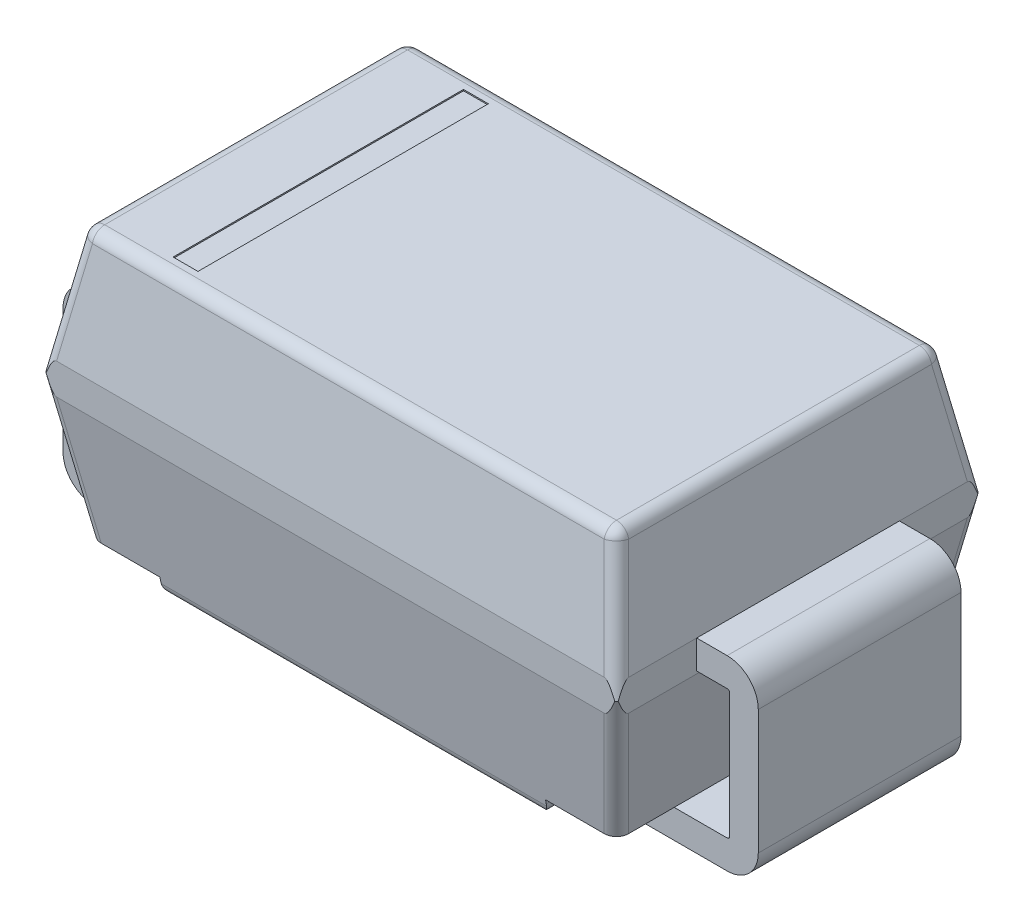
SolidWorks part; units mm, degrees
ref_plane "Front Plane" through (0, 0, 0) normal (0, 0, 1) x (1, 0, 0)
ref_plane "Top Plane" through (0, 0, 0) normal (0, 1, 0) x (1, 0, 0)
ref_plane "Right Plane" through (0, 0, 0) normal (1, 0, 0) x (0, 0, -1)
sketch "Sketch5" plane through (0, 0, 0) normal (0, 0, 1) x (1, 0, 0)
  line L0 (-2.3, 0.3724) -> (-2.3, 0.1224)
  line L1 (-2.3, 0.3724) -> (-2.1413, 1.2724)
  line L2 (2.3, 0.3724) -> (2.3, 0.1224)
  line L3 (0, 0) -> (-0.663, 0) construction
  line L4 (-2.3, 0.1224) -> (-2.1204, -0.896)
  line L5 (2.3, 0.1224) -> (2.1204, -0.896)
  line L6 (2.3, 0.3724) -> (2.1413, 1.2724)
  line L7 (2.3, 0.3724) -> (2.3, 0.1224)
  line L8 (0, 0) -> (0, 0.4546) construction
  line L9 (-2.3, 0.1224) -> (-1.6581, 0.1224) construction
  line L10 (2.1413, 1.2724) -> (-2.1413, 1.2724)
  line L11 (-2.1204, -0.896) -> (-1.55, -0.896)
  line L12 (1.55, -1.0276) -> (-1.55, -1.0276)
  line L13 (-2.3, 0.3724) -> (-2.3, 0.1224)
  line L14 (-1.55, -0.896) -> (-1.55, -1.0276)
  line L15 (1.55, -0.896) -> (1.55, -1.0276)
  line L16 (2.1204, -0.896) -> (1.55, -0.896)
  line L17 (-0.6495, -1.1276) -> (-0.7495, -1.1276) construction
  dimension "D1" = 0.75
  dimension "D2" = 0.1315
  dimension "D3" = 0.25
  dimension "D4" = 10
  dimension "D5" = 10
  dimension "BodyLength" = 4.6
  dimension "D6" = 10
  dimension "D7" = 10
  dimension "Height" = 2.4
  dimension "A1" = 0.1
extrude "Extrude2" add sketch "Sketch5" along normal mid plane 2.92 contours L12 L5 L2 L6 L10 L1 L0 L4 region at (0, 0.144, 0)
sketch "Sketch15" plane through (0, 0, 0) normal (1, 0, 0) x (0, 0, -1)
  line L0 (1.1543, -1.6111) -> (1.46, 0.1224)
  line L1 (1.46, 0.1224) -> (1.46, 0.3724)
  line L2 (1.46, 0.3724) -> (1.1334, 2.2248)
  dimension "D1" = 10
  dimension "D2" = 10
extrude "Extrude10" cut sketch "Sketch15" against normal through all and the other way through all flip side to cut
mirror "Mirror1" about plane through (0, 0, 0) normal (0, 0, 1) of "Extrude10"
sketch "Sketch9" plane through (0, 0, 0) normal (0, 0, 1) x (1, 0, 0)
  line L0 (-2.3, 0.3724) -> (-2.545, 0.3724)
  line L1 (-2.795, 0.1224) -> (-2.795, -0.8776)
  line L2 (-2.545, -1.1276) -> (-1.275, -1.1276)
  line L3 (-2.3, 0.1424) -> (-2.545, 0.1424)
  line L4 (-2.565, 0.1224) -> (-2.565, -0.8776)
  line L5 (-2.545, -0.8976) -> (-1.275, -0.8976)
  line L6 (-1.275, -0.8976) -> (-1.275, -1.1276)
  line L7 (-2.3, 0.3724) -> (-2.3, 0.1424)
  line L8 (0, 0) -> (0, -0.4455) construction
  line L9 (2.3, 0.3724) -> (2.3, 0.1424)
  line L10 (1.275, -0.8976) -> (1.275, -1.1276)
  line L11 (2.545, -0.8976) -> (1.275, -0.8976)
  line L12 (2.565, 0.1224) -> (2.565, -0.8776)
  line L13 (2.3, 0.1424) -> (2.545, 0.1424)
  line L14 (2.545, -1.1276) -> (1.275, -1.1276)
  line L15 (2.795, 0.1224) -> (2.795, -0.8776)
  line L16 (2.3, 0.3724) -> (2.545, 0.3724)
  arc A0 (-2.545, 0.3724) -> (-2.795, 0.1224) centre (-2.545, 0.1224) ccw
  arc A1 (-2.795, -0.8776) -> (-2.545, -1.1276) centre (-2.545, -0.8776) ccw
  arc A2 (-2.545, 0.1424) -> (-2.565, 0.1224) centre (-2.545, 0.1224) ccw
  arc A3 (-2.565, -0.8776) -> (-2.545, -0.8976) centre (-2.545, -0.8776) ccw
  arc A4 (2.565, -0.8776) -> (2.545, -0.8976) centre (2.545, -0.8776) cw
  arc A5 (2.545, 0.1424) -> (2.565, 0.1224) centre (2.545, 0.1224) cw
  arc A6 (2.795, -0.8776) -> (2.545, -1.1276) centre (2.545, -0.8776) cw
  arc A7 (2.545, 0.3724) -> (2.795, 0.1224) centre (2.545, 0.1224) cw
  dimension "D1" = 0.25
  dimension "TotalLength" = 5.59
  dimension "PinLength" = 1.52
  dimension "C" = 0.23
extrude "Extrude6" add sketch "Sketch9" along normal mid plane 1.63
fillet "Fillet1" radius 0.1 28 edges at (0, -1.0276, -1.2572) (-1.55, -1.0276, 1.0361) (-1.55, -1.0276, -1.0361) (0, -1.0276, 1.2572) (1.55, -1.0276, 1.0361) (1.55, -1.0276, -1.0361) (-2.1413, 1.2724, 0) (0, 1.2724, -1.3013) (2.1413, 1.2724, 0) (0, 1.2724, 1.3013) (-2.2102, -0.3868, -1.3702) (-2.2207, 0.8224, -1.3807) (-2.2207, 0.8224, 1.3807) (-2.2102, -0.3868, 1.3702) (2.2102, -0.3868, 1.3702) (2.2207, 0.8224, 1.3807) (2.2102, -0.3868, -1.3702) (2.2207, 0.8224, -1.3807) (1.55, -0.9626, -0.815) (-1.55, -0.9626, -0.815) (-1.55, -0.9626, 0.815) (1.55, -0.9626, 0.815) (1.4125, -1.0276, -0.815) (-1.4125, -1.0276, -0.815) (-1.275, -1.0276, 0) (-1.4125, -1.0276, 0.815) (1.4125, -1.0276, 0.815) (1.275, -1.0276, 0)
sketch "Sketch17" plane through (0, 1.2724, 0) normal (0, 1, 0) x (1, 0, 0)
  line L0 (-2.0574, 1.2174) -> (-2.0574, -1.2174) construction
  line L1 (-1.5574, 1.1674) -> (-1.3574, 1.1674)
  line L2 (-1.5574, 1.1674) -> (-1.5574, -1.1674)
  line L3 (-1.5574, -1.1674) -> (-1.3574, -1.1674)
  line L4 (-1.3574, 1.1674) -> (-1.3574, -1.1674)
  line L5 (2.0574, 1.2174) -> (-2.0574, 1.2174) construction
  line L6 (0, 0) -> (-0.2283, 0) construction
  dimension "D1" = 0.2
  dimension "D2" = 0.5
  dimension "D3" = 0.05
extrude "Extrude11" cut sketch "Sketch17" against normal blind 0.01
